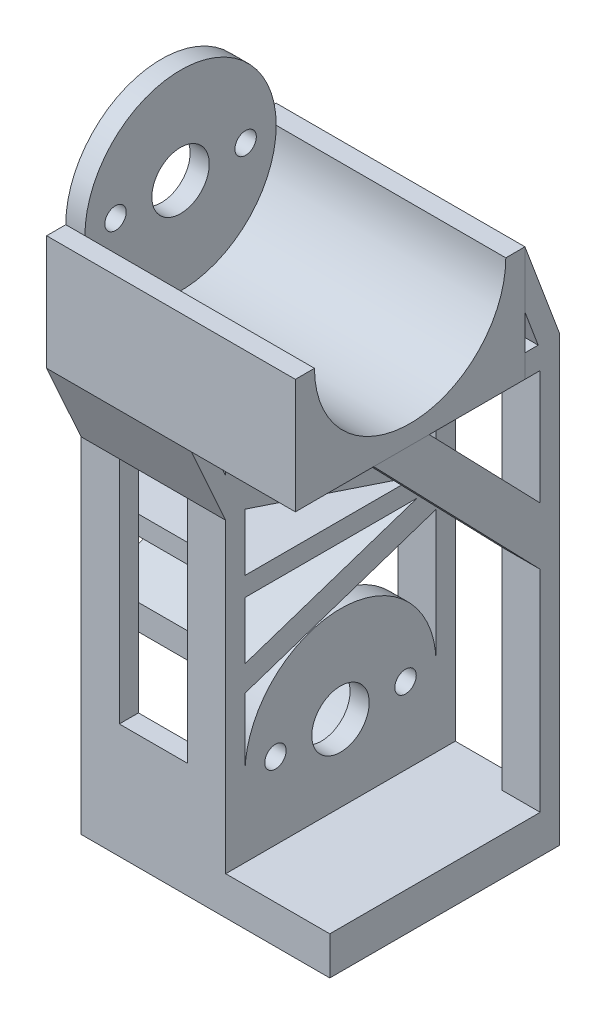
SolidWorks part; units mm, degrees
material "PLA"
ref_plane "Front Plane" through (0, 0, 0) normal (0, 0, 1) x (1, 0, 0)
ref_plane "Top Plane" through (0, 0, 0) normal (0, 1, 0) x (1, 0, 0)
ref_plane "Right Plane" through (0, 0, 0) normal (1, 0, 0) x (0, 0, -1)
sketch "Sketch1" plane through (0, 0, 0) normal (1, 0, 0) x (0, 0, -1)
  line L1 (55, 0) -> (-55, 0) construction
  circle A0 centre (0, 0) radius 12.5
  circle A1 centre (0, 0) radius 3.75
  circle A2 centre (8.5, 0) radius 1.4
  circle A3 centre (-8.5, 0) radius 1.4
  dimension "D1" = 25
  dimension "D2" = 7.5
  dimension "D3" = 2.8
  dimension "D5" = 8.5
  dimension "D4" = 17
extrude "Boss-Extrude1" add sketch "Sketch1" along normal blind 2.5
ref_plane "Plane1" through (-11.4, 0, 0) normal (-1, 0, 0) x (0, 0, 1)
sketch "Sketch4" plane through (-11.4, 0, 0) normal (-1, 0, 0) x (0, 0, 1)
  circle A0 centre (0, 55) radius 12.5
  circle A1 centre (0, 55) radius 3.75
  circle A3 centre (8.5, 55) radius 1.4
  circle A4 centre (-8.5, 55) radius 1.4
  circle A5 centre (-8.5, 0) radius 1.4 construction
  circle A6 centre (0, 0) radius 12.5 construction
  dimension "D1" = 25
  dimension "D2" = 3.75
  dimension "D3" = 55
  dimension "D4" = 2.8
  dimension "D5" = 2.8
  dimension "D6" = 8.5
  dimension "D7" = 8.5
  dimension "D8" = 8.5
extrude "Boss-Extrude3" [suppressed] add sketch "Sketch4" along normal blind 2.5 separate body
sketch "Sketch2" plane through (2.5, 0, 0) normal (1, 0, 0) x (0, 0, -1)
  line L0 (55, 0) -> (-55, 0) construction
  line L1 (-12.5, 0) -> (-15.5, 0)
  line L2 (-15.5, 0) -> (-15.5, -15)
  line L3 (-15.5, -15) -> (15.5, -15)
  line L4 (15.5, -15) -> (15.5, 0)
  line L5 (15.5, 0) -> (12.5, 0)
  arc A0 (12.5, 0) -> (-12.5, 0) centre (0, 0) cw
  circle A1 centre (0, 0) radius 12.5 construction
  dimension "D1" = 3
  dimension "D2" = 15
  dimension "D3" = 31
extrude "Boss-Extrude2" [suppressed] add sketch "Sketch2" against normal up to surface (16.4 mm away) up to face at (2.5, 0, -9.9)
sketch "Sketch5" [suppressed] plane through (-13.9, 0, 0) normal (-1, 0, 0) x (0, 0, 1)
  line L0 (-12.5, 55) -> (-15.5, 55)
  line L1 (-15.5, 55) -> (-15.5, 40)
  line L2 (-15.5, 40) -> (15.5, 40)
  line L3 (15.5, 40) -> (15.5, 55)
  line L4 (15.5, 55) -> (12.5, 55)
  circle A0 centre (0, 55) radius 12.5 construction
  arc A1 (12.5, 55) -> (-11.4248, 49.9282) centre (0, 55) cw
  circle M2 centre (0, 55) radius 12.5
  dimension "D1" = 3
  dimension "D2" = 15
  dimension "D3" = 31
extrude "Boss-Extrude4" [suppressed] add sketch "Sketch5" against normal up to surface (16.4 mm away) contours L3 L4 L0 L1 L2 M2 up to face at (2.5, 0, -9.9)
sketch "Sketch6" [suppressed] plane through (0, 0, -15.5) normal (0, 0, -1) x (-1, 0, 0)
  line L0 (0, 30.8257) -> (3.6093, 17.5806)
  line L1 (55, 0) -> (-55, 0) construction
  line L2 (8.4, 0) -> (13.9, 0)
  line L3 (13.9, -15) -> (13.9, 0) construction
  line L4 (11.4, -1.8349) -> (6.4117, 16.4708)
  line L5 (0, 44.7868) -> (0, -44.7868) construction
  line L6 (-2.5, 40) -> (13.9, 40) construction
  line L7 (0, 40) -> (-2.5, 40)
  line L8 (0, 7.1942) -> (3.6093, 17.5806)
  line L9 (11.4, 30.8257) -> (11.4, -1.8349)
  line L10 (11.4, 40) -> (13.9, 40)
  line L11 (11.4, 30.8257) -> (6.4117, 16.4708)
  line L12 (0.6881, 0) -> (-2.5, 0)
  line L13 (5.0105, 12.4386) -> (8.4, 0)
  line L14 (5.0105, 21.6129) -> (11.4, 40)
  line L15 (5.0105, 21.6129) -> (0, 40)
  line L16 (5.0105, 12.4386) -> (0.6881, 0)
  line L17 (11.4, -43.6537) -> (11.4, 43.6537) construction
  line L18 (13.9, 0) -> (31.9, 0)
  line L19 (13.9, 0) -> (13.9, 40)
  line L20 (13.9, 40) -> (11.4, 40)
  line L21 (13.9, 0) -> (13.9, 40)
  line L22 (0.6881, 0) -> (-2.5, 0)
  line L23 (0, 7.1942) -> (0, 30.8257)
  line L24 (0, 40) -> (-2.5, 40)
  line L25 (-2.5, 0) -> (-2.5, 40)
  line M23 (13.9, 0) -> (-2.5, 0)
extrude "Boss-Extrude5" [suppressed] add sketch "Sketch6" against normal blind 3 contours L25 L16 L13 L19 L10 L14 L15 L7 L21 L4 L11 L8 L23 L0 M23
mirror "Mirror1" [suppressed] about plane through (0, 0, 0) normal (0, 0, 1)
sketch "Sketch7" [suppressed] plane through (0, -15, 0) normal (0, -1, 0) x (-1, 0, 0)
  line L1 (-0.4, 12.36) -> (-9.4, 12.36)
  line L3 (-0.4, 9.36) -> (-9.4, 9.36)
  line L5 (-0.4, -2.64) -> (-9.4, -2.64)
  line L7 (-0.4, 0.36) -> (-9.4, 0.36)
  line L9 (13.9, 15.5) -> (-2.5, 15.5) construction
  line L10 (13.9, -15.5) -> (13.9, 15.5) construction
  arc A0 (-0.4, 9.36) -> (-0.4, 12.36) centre (-0.4, 10.86) ccw
  arc A1 (-0.4, -2.64) -> (-0.4, 0.36) centre (-0.4, -1.14) ccw
  arc A2 (-9.4, 0.36) -> (-9.4, -2.64) centre (-9.4, -1.14) ccw
  arc A3 (-9.4, 12.36) -> (-9.4, 9.36) centre (-9.4, 10.86) ccw
  dimension "D3" = 1.5
  dimension "D1" = 12
  dimension "D2" = 23.3
  dimension "D5" = 3.14
extrude "Boss-Extrude6" [suppressed] add sketch "Sketch7" along normal blind 5
sketch "Sketch8" [suppressed] plane through (2.5, 0, 0) normal (1, 0, 0) x (0, 0, -1)
  line L0 (15.5, -15) -> (15.5, 55) construction
  line L1 (-15.5, -15) -> (15.5, -15)
  line L2 (-15.5, -15) -> (-15.5, -10)
  line L3 (-15.5, -10) -> (15.5, -10)
  line L4 (15.5, -15) -> (15.5, -10)
  dimension "D1" = 5
extrude "Boss-Extrude7" [suppressed] add sketch "Sketch8" along normal blind 17
sketch "Sketch10" [suppressed] plane through (0, -10, 0) normal (0, 1, 0) x (1, 0, 0)
  line L1 (19.5, 15.5) -> (16.5, 15.5)
  line L2 (19.5, 15.5) -> (19.5, 12.5)
  line L3 (19.5, 12.5) -> (16.5, 12.5)
  line L4 (16.5, 15.5) -> (16.5, 12.5)
  dimension "D1" = 3
extrude "Boss-Extrude8" [suppressed] add sketch "Sketch10" along normal up to surface (65 mm away)
sketch "Sketch11" [suppressed] plane through (2.5, 0, 0) normal (1, 0, 0) x (0, 0, -1)
  line L0 (-12.5, 55) -> (-15.5, 55)
  line L1 (-15.5, 55) -> (-15.5, 40)
  line L2 (-15.5, 55) -> (-15.5, -10) construction
  line L3 (-15.5, 40) -> (15.5, 40)
  line L4 (15.5, 40) -> (15.5, 55)
  line L5 (15.5, 55) -> (12.5, 55)
  arc A0 (12.5, 55) -> (-12.5, 55) centre (0, 55) cw
  arc A1 (-12.5, 55) -> (12.5, 55) centre (0, 55) ccw construction
  dimension "D1" = 15
extrude "Boss-Extrude9" [suppressed] add sketch "Sketch11" along normal blind 17
sketch "Sketch12" [suppressed] plane through (19.5, 0, 0) normal (1, 0, 0) x (0, 0, -1)
  line L0 (-15.5, 40) -> (12.5, 15)
  line L1 (12.5, 40) -> (12.5, -10) construction
  line L2 (12.5, 15) -> (12.5, 20)
  line L3 (12.5, 20) -> (-9.9, 40)
  line L4 (-15.5, 40) -> (12.5, 40) construction
  line L5 (-9.9, 40) -> (-15.5, 40)
  dimension "D1" = 5
extrude "Boss-Extrude10" [suppressed] add sketch "Sketch12" against normal blind 3
sketch "Sketch13" [suppressed] plane through (-13.9, 0, 0) normal (-1, 0, 0) x (0, 0, 1)
  line L0 (-12.5, 15) -> (0, 26.1607)
  line L1 (12.5, 0) -> (12.5, 40) construction
  line L2 (15.5, 40) -> (-12.5, 15) construction
  line L3 (12.5, 37.3214) -> (12.5, 40)
  line L4 (12.5, 40) -> (9.9, 40)
  line L5 (-12.5, 40) -> (12.5, 40) construction
  line L6 (9.9, 40) -> (15.5, 40) construction
  line L7 (9.9, 40) -> (0, 31.1607)
  line L8 (-12.5, 20) -> (-12.5, 15)
  line L9 (12.5, 15) -> (0, 26.1607)
  line L10 (-12.5, 0) -> (-12.5, 40) construction
  line L11 (-12.5, 37.3214) -> (-12.5, 40)
  line L12 (12.5, 20) -> (2.8, 28.6607)
  line L13 (-9.9, 40) -> (-12.5, 40)
  line L14 (12.5, 20) -> (12.5, 15)
  line L15 (-2.8, 28.6607) -> (-12.5, 37.3214)
  line L16 (-2.8, 28.6607) -> (-12.5, 20)
  line L17 (2.8, 28.6607) -> (12.5, 37.3214)
  line L18 (0, 31.1607) -> (-9.9, 40)
extrude "Boss-Extrude11" [suppressed] add sketch "Sketch13" against normal blind 2.5
pattern_linear "LPattern1" [suppressed] count 2 spacing 13.9 of bodies 125
sketch "Sketch14" plane through (-11.4, 0, 0) normal (-1, 0, 0) x (0, 0, 1)
  line L0 (0, -44.2539) -> (0, 44.2539) construction
  circle A0 centre (4.5, 55) radius 12.5
  circle A2 centre (0, 0) radius 12.5 construction
  circle A4 centre (4.5, 55) radius 3.75
  circle A6 centre (-4, 55) radius 1.4
  circle A7 centre (13, 55) radius 1.4
  circle A8 centre (8.5, 0) radius 1.4 construction
  dimension "D1" = 25
  dimension "D3" = 7.5
  dimension "D4" = 8.5
  dimension "D5" = 8.5
  dimension "D6" = 4.5
  dimension "D2" = 55
extrude "Boss-Extrude12" add sketch "Sketch14" along normal blind 2.5 from offset 2.5
sketch "Sketch15" plane through (0, 0, 0) normal (-1, 0, 0) x (0, 0, 1)
  line L0 (55, 0) -> (-55, 0) construction
  line L1 (0, -44.2539) -> (0, 44.2539) construction
  line L2 (-15, -15) -> (15, -15)
  line L3 (-15, -15) -> (-15, 0)
  line L4 (-15, 0) -> (-12.5, 0)
  line L5 (15, -15) -> (15, 0)
  line L6 (-15, -15) -> (15, 0) construction
  line L7 (-15, 0) -> (15, -15) construction
  line L8 (12.5, 0) -> (15, 0)
  arc A0 (-12.5, 0) -> (12.5, 0) centre (0, 0) ccw
  circle A1 centre (0, 0) radius 12.5 construction
  point P8 (0, -7.5)
  dimension "D2" = 15
  dimension "D1" = 15
extrude "Boss-Extrude13" add sketch "Sketch15" along normal up to surface (16.4 mm away) and the other way up to surface (2.5 mm away) up to face at (-16.4, 55, 8.25) other way up to face at (2.5, 0, -9.9)
sketch "Sketch16" plane through (-13.9, 0, 0) normal (1, 0, 0) x (0, 0, -1)
  line L0 (-17, 55) -> (-19.5, 55)
  line L1 (-19.5, 55) -> (-19.5, 40)
  line L2 (-19.5, 40) -> (10.5, 40)
  line L3 (10.5, 40) -> (10.5, 55)
  line L4 (10.5, 55) -> (8, 55)
  arc A0 (8, 55) -> (-17, 55) centre (-4.5, 55) cw
  circle A1 centre (-4.5, 55) radius 12.5 construction
  dimension "D1" = 2.5
  dimension "D2" = 2.5
  dimension "D3" = 15
extrude "Boss-Extrude14" add sketch "Sketch16" along normal blind 30 and the other way up to surface (2.5 mm away) other way up to face at (-16.4, 55, 8.25)
sketch "Sketch17" plane through (0, 0, 0) normal (0, 1, 0) x (1, 0, 0)
  line L0 (-16.4, 12.5) -> (-16.4, 15) construction
  line L1 (-16.4, 15) -> (-11.4, 15)
  line L2 (-16.4, 15) -> (-16.4, 12.5)
  line L3 (-16.4, 12.5) -> (-11.4, 12.5)
  line L4 (-11.4, 15) -> (-11.4, 12.5)
  line L5 (-16.4, 15) -> (2.5, 15) construction
  line L6 (-16.4, 12.5) -> (0, 12.5) construction
  line L7 (-11.4, 43.6537) -> (-11.4, -43.6537) construction
  line L9 (2.5, 15) -> (-2.5, 15)
  line L10 (2.5, 15) -> (2.5, 12.5)
  line L11 (2.5, 12.5) -> (-2.5, 12.5)
  line L12 (-2.5, 15) -> (-2.5, 12.5)
extrude "Boss-Extrude15" add sketch "Sketch17" along normal up to surface (40 mm away) up to face at (-0.15, 40, 4.5)
sketch "Sketch19" plane through (0, 0, 0) normal (0, 1, 0) x (1, 0, 0)
  line L0 (-11.4, 43.6537) -> (-11.4, -43.6537) construction
  line L1 (-16.4, -15) -> (-11.4, -15)
  line L2 (-16.4, -15) -> (-16.4, -12.5)
  line L3 (-16.4, -12.5) -> (-11.4, -12.5)
  line L4 (-11.4, -15) -> (-11.4, -12.5)
  line L5 (-16.4, -12.5) -> (0, -12.5) construction
  line L7 (2.5, -15) -> (-2.5, -15)
  line L8 (2.5, -15) -> (2.5, -12.5)
  line L9 (2.5, -12.5) -> (-2.5, -12.5)
  line L10 (-2.5, -15) -> (-2.5, -12.5)
extrude "Boss-Extrude16" add sketch "Sketch19" along normal up to surface (40 mm away) up to face at (-0.15, 40, 4.5)
sketch "Sketch20" plane through (2.5, 0, 0) normal (1, 0, 0) x (0, 0, -1)
  line L1 (15, 40) -> (10.5, 40)
  line L2 (15, 40) -> (15, 43)
  line L3 (12.2314, 43) -> (10.5, 43)
  line L4 (10.5, 40) -> (10.5, 43)
  line L5 (15, 43) -> (10.5, 55)
  line L6 (10.5, 55) -> (10.5, 47.6171)
  line L7 (10.5, 47.6171) -> (12.2314, 43)
  line L8 (10.5, 40) -> (10.5, 55) construction
  line L9 (15, 40) -> (15, -15) construction
  dimension "D1" = 3
extrude "Boss-Extrude17" add sketch "Sketch20" against normal up to surface (18.9 mm away) and the other way up to surface (13.6 mm away) up to face at (-16.4, 55, 8.25) other way up to face at (16.1, 47.9167, 4.5)
sketch "Sketch22" plane through (2.5, 0, 0) normal (1, 0, 0) x (0, 0, -1)
  line L0 (-12.5, 40) -> (-12.5, 0) construction
  line L1 (-12.5, 20) -> (10, 20)
  line L2 (-12.5, 20) -> (-12.5, 22.5)
  line L3 (-12.5, 22.5) -> (10, 22.5)
  line L4 (12.5, 20) -> (12.5, 22.5)
  line L5 (12.5, 40) -> (12.5, 0) construction
  line L6 (-12.5, 30) -> (10, 22.5)
  line L7 (-10, 32.5) -> (12.5, 32.5)
  line L8 (-12.5, 32.5) -> (-12.5, 35)
  line L9 (-12.5, 35) -> (12.5, 35)
  line L10 (12.5, 32.5) -> (12.5, 35)
  line L11 (-12.5, 30) -> (-12.5, 32.5)
  line L12 (12.5, 25) -> (-10, 32.5)
  line L13 (12.5, 25) -> (12.5, 22.5)
  line L14 (10, 20) -> (-12.5, 12.5)
  line L15 (-12.5, 12.5) -> (-12.5, 9.1667)
  line L16 (12.5, 20) -> (12.5, 17.5)
  line L17 (12.5, 17.5) -> (-12.5, 9.1667)
  arc A0 (12.5, 0) -> (-12.5, 0) centre (0, 0) ccw construction
  dimension "D10" = 7.5
  dimension "D1" = 2.5
  dimension "D2" = 20
  dimension "D3" = 10
  dimension "D4" = 2.5
  dimension "D5" = 2.5
  dimension "D6" = 2.5
  dimension "D7" = 2.5
  dimension "D8" = 2.5
  dimension "D9" = 2.5
extrude "Boss-Extrude19" add sketch "Sketch22" against normal up to surface (18.9 mm away) up to face at (-16.4, 55, 8.25)
sketch "Sketch23" plane through (-16.4, 0, 0) normal (-1, 0, 0) x (0, 0, 1)
  line L0 (19.5, 40) -> (15, 30)
  line L2 (15, 30) -> (15, 35)
  line L3 (15, 35) -> (17.25, 40)
  line L4 (19.5, 40) -> (-10.5, 40) construction
  line L5 (17.25, 40) -> (19.5, 40)
  line L6 (15, -15) -> (15, 40) construction
extrude "Boss-Extrude20" add sketch "Sketch23" against normal up to surface (18.9 mm away) up to face at (2.5, 30, -5)
sketch "Sketch24" plane through (2.5, 0, 0) normal (1, 0, 0) x (0, 0, -1)
  line L0 (15, 40) -> (15, -15) construction
  line L1 (-15, -15) -> (15, -15)
  line L2 (-15, -15) -> (-15, -10)
  line L3 (-15, -10) -> (15, -10)
  line L4 (15, -15) -> (15, -10)
  dimension "D1" = 5
extrude "Boss-Extrude21" add sketch "Sketch24" along normal up to surface (13.6 mm away) up to face at (16.1, 47.9167, 4.5)
sketch "Sketch25" plane through (16.1, 0, 0) normal (1, 0, 0) x (0, 0, -1)
  line L0 (-19.5, 40) -> (10.5, 40) construction
  line L1 (15, -10) -> (12.5, -10)
  line L2 (15, -10) -> (15, 40)
  line L3 (15, 40) -> (12.5, 40)
  line L4 (12.5, -10) -> (12.5, 40)
  line L5 (15, 40) -> (10.5, 40) construction
extrude "Boss-Extrude22" add sketch "Sketch25" against normal blind 5
sketch "Sketch26" plane through (16.1, 0, 0) normal (1, 0, 0) x (0, 0, -1)
  line L0 (-9.2591, 40) -> (12.5, 17.5)
  line L1 (12.5, 17.5) -> (12.5, 25)
  line L2 (12.5, 40) -> (12.5, -10) construction
  line L3 (12.5, 25) -> (-10, 32.5) construction
  line L4 (12.5, 25) -> (-2.0061, 40)
  line L5 (-19.5, 40) -> (10.5, 40) construction
  line L6 (-2.0061, 40) -> (-9.2591, 40)
extrude "Boss-Extrude23" add sketch "Sketch26" against normal blind 5
